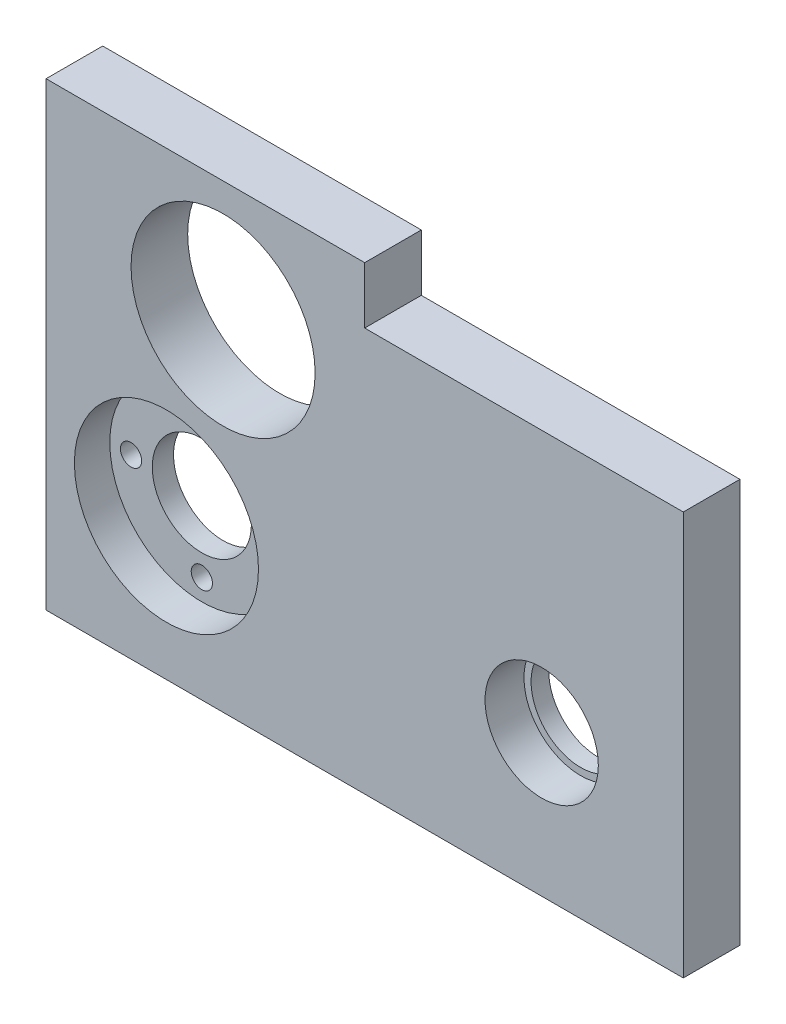
SolidWorks part; units mm, degrees
ref_plane "Front" through (0, 0, 0) normal (0, 0, 1) x (1, 0, 0)
ref_plane "Top" through (0, 0, 0) normal (0, 1, 0) x (1, 0, 0)
ref_plane "Right" through (0, 0, 0) normal (1, 0, 0) x (0, 0, -1)
sketch "Esquisse1" plane through (0, 0, 0) normal (0, 0, 1) x (1, 0, 0)
  line L1 (0, 0) -> (90, 0)
  line L2 (0, 0) -> (0, 65)
  line L3 (0, 65) -> (90, 65)
  line L4 (90, 0) -> (90, 65)
  circle A0 centre (70, 20) radius 7
  circle A1 centre (17, 20) radius 13
  circle A2 centre (25, 48) radius 13
  dimension "D3" = 14
  dimension "D4" = 20
  dimension "D6" = 53
  dimension "D8" = 26
  dimension "D9" = 26
  dimension "D1" = 90
  dimension "D2" = 65
  dimension "D5" = 70
  dimension "D7" = 20
  dimension "D10" = 53
  dimension "D11" = 48
extrude "Boss.-Extru.1" add sketch "Esquisse1" along normal blind 8
sketch "Esquisse2" plane through (0, 0, 0) normal (0, 0, -1) x (-1, 0, 0)
  circle A0 centre (-17, 20) radius 13
  circle A1 centre (-17, 20) radius 13 construction
extrude "Boss.-Extru.2" add sketch "Esquisse2" against normal blind 3
sketch "Esquisse3" plane through (0, 0, 3) normal (0, 0, 1) x (1, 0, 0)
  line L0 (27, 20) -> (17, 20) construction
  circle A0 centre (17, 20) radius 7
  circle A1 centre (27, 20) radius 1.5
  circle A2 centre (17, 10) radius 1.5
  circle A3 centre (7, 20) radius 1.5
  circle A4 centre (17, 30) radius 1.5
  point P13 (17, 20)
  dimension "D1" = 14
  dimension "D2" = 3
  dimension "D3" = 10
  dimension "D4" = 4
extrude "Enlèv. mat.-Extru.1" cut sketch "Esquisse3" against normal through all
sketch "Esquisse4" plane through (0, 0, 8) normal (0, 0, 1) x (1, 0, 0)
  circle A0 centre (70, 20) radius 8
  dimension "D1" = 16
extrude "Enlèv. mat.-Extru.2" cut sketch "Esquisse4" against normal blind 5.5
sketch "Esquisse5" plane through (0, 0, 8) normal (0, 0, 1) x (1, 0, 0)
  line L0 (90, 65) -> (0, 65) construction
  line L1 (45, 65) -> (90, 65)
  line L2 (45, 65) -> (45, 57)
  line L3 (45, 57) -> (90, 57)
  line L4 (90, 65) -> (90, 57)
  line L5 (90, 0) -> (90, 65) construction
  dimension "D1" = 8
  dimension "D2" = 45
extrude "Enlèv. mat.-Extru.3" cut sketch "Esquisse5" against normal through all
